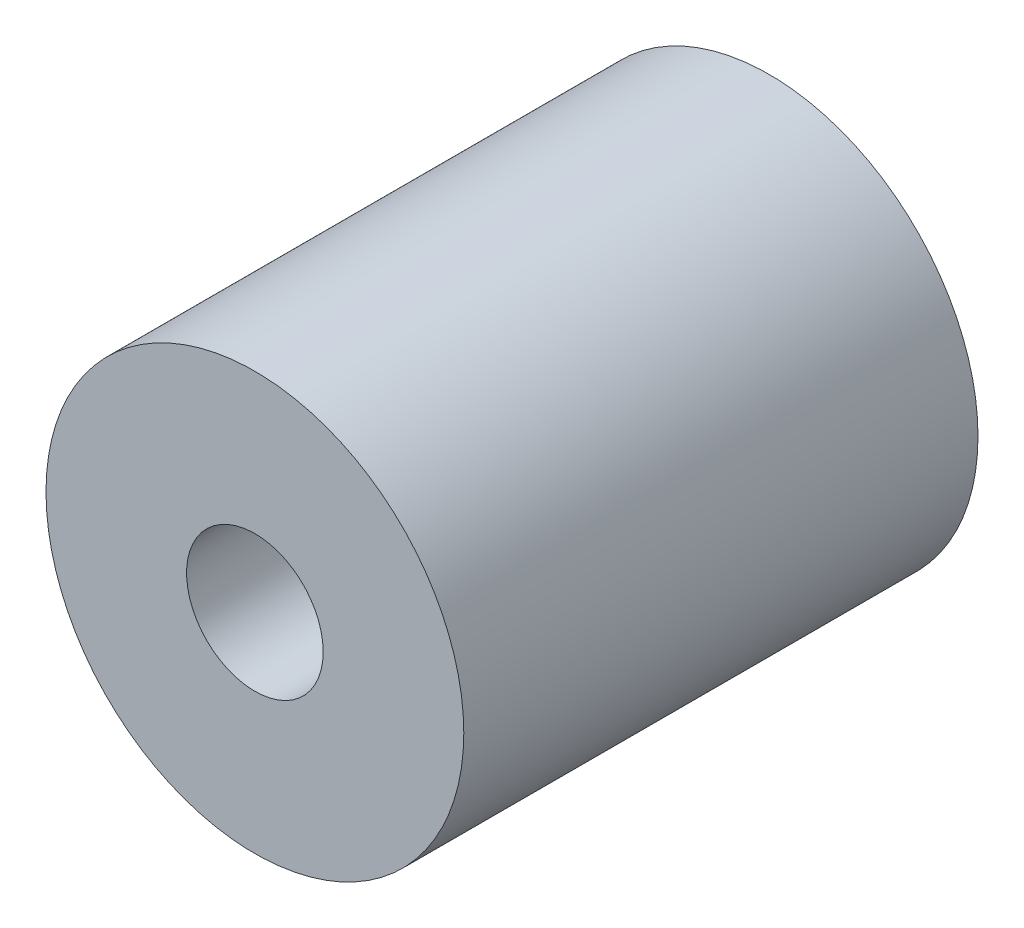
SolidWorks part; units mm, degrees
ref_plane "Front Plane" through (0, 0, 0) normal (0, 0, 1) x (1, 0, 0)
ref_plane "Top Plane" through (0, 0, 0) normal (0, 1, 0) x (1, 0, 0)
ref_plane "Right Plane" through (0, 0, 0) normal (1, 0, 0) x (0, 0, -1)
sketch "Sketch1" plane through (0, 0, 0) normal (0, 1, 0) x (1, 0, 0)
  line L0 (2.125, -3.75) -> (6.5, -3.75)
  line L1 (6.5, -3.75) -> (6.5, 0)
  line L2 (6.5, 0) -> (2.125, 0)
  line L3 (2.125, 0) -> (2.125, -3.75)
  line L4 (0, 0) -> (0, -3.75) construction
  dimension "D1" = 2.125
  dimension "D2" = 6.5
  dimension "D3" = 3.75
revolve "Revolve1" add sketch "Sketch1" angle 360 about L4 reverse direction yes
sketch "Sketch2" plane through (0, 0, 3.75) normal (0, 0, 1) x (1, 0, 0)
  circle A0 centre (0, 0) radius 2.125
  circle A1 centre (0, 0) radius 6.5
  circle A2 centre (0, 0) radius 6.5 construction
  dimension "D1" = 4.25
extrude "Boss-Extrude1" add sketch "Sketch2" along normal blind 12.25
sketch "Sketch3" plane through (0, 0, 0) normal (0, 0, -1) x (-1, 0, 0)
  circle A0 centre (0, 0) radius 3
  circle A1 centre (0, 0) radius 6.5
  circle A2 centre (0, 0) radius 6.5
  dimension "D2" = 6
  dimension "D1" = 0
extrude "Cut-Extrude1" [suppressed] cut sketch "Sketch3" against normal blind 0.5
